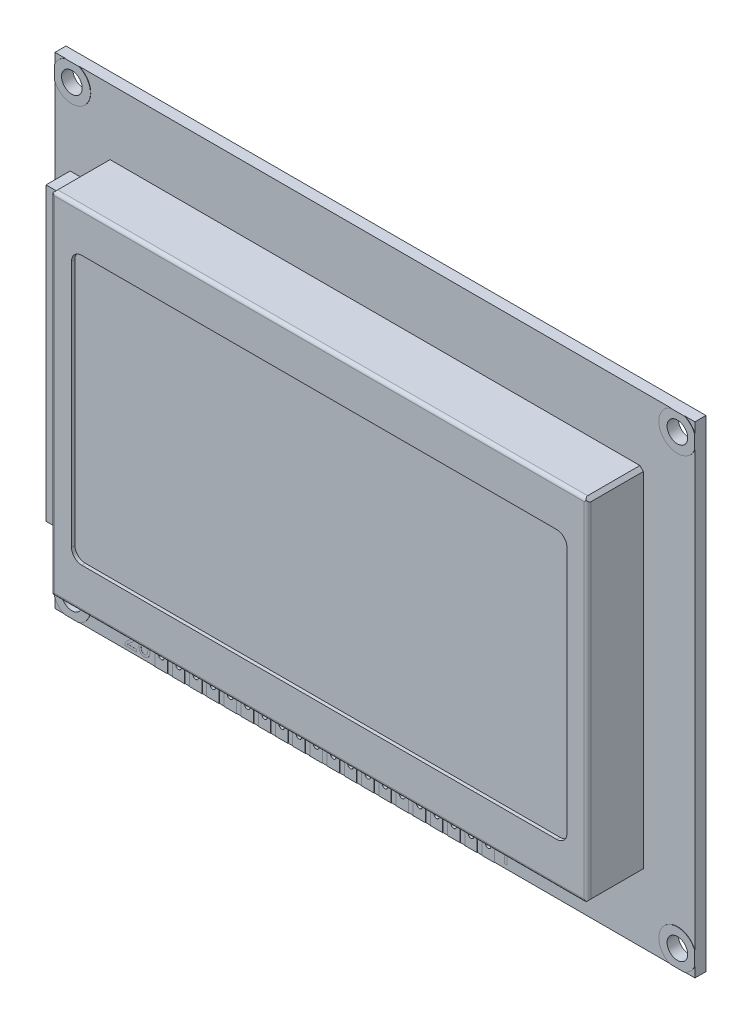
SolidWorks part; units mm, degrees
ref_plane "Front Plane" through (0, 0, 0) normal (0, 0, 1) x (1, 0, 0)
ref_plane "Top Plane" through (0, 0, 0) normal (0, 1, 0) x (1, 0, 0)
ref_plane "Right Plane" through (0, 0, 0) normal (1, 0, 0) x (0, 0, -1)
sketch "Szkic2" plane through (0, 0, 0) normal (0, 0, 1) x (1, 0, 0)
  line L1 (-46.5, -35) -> (46.5, -35)
  line L2 (-46.5, -35) -> (-46.5, 35)
  line L3 (-46.5, 35) -> (46.5, 35)
  line L4 (46.5, -35) -> (46.5, 35)
  line L5 (-46.5, -35) -> (46.5, 35) construction
  line L6 (-46.5, 35) -> (46.5, -35) construction
  circle A0 centre (-44, -32.5) radius 1.5
  circle A1 centre (44, -32.5) radius 1.5
  circle A2 centre (44, 32.5) radius 1.5
  circle A3 centre (-44, 32.5) radius 1.5
  circle A4 centre (16.5, -33.25) radius 0.4
  circle A5 centre (14, -33.25) radius 0.4
  circle A6 centre (11.5, -33.25) radius 0.4
  circle A7 centre (9, -33.25) radius 0.4
  circle A8 centre (6.5, -33.25) radius 0.4
  circle A9 centre (4, -33.25) radius 0.4
  circle A10 centre (1.5, -33.25) radius 0.4
  circle A11 centre (-1, -33.25) radius 0.4
  circle A12 centre (-3.5, -33.25) radius 0.4
  circle A13 centre (-6, -33.25) radius 0.4
  circle A14 centre (-8.5, -33.25) radius 0.4
  circle A15 centre (-11, -33.25) radius 0.4
  circle A16 centre (-13.5, -33.25) radius 0.4
  circle A17 centre (-16, -33.25) radius 0.4
  circle A18 centre (-18.5, -33.25) radius 0.4
  circle A19 centre (-21, -33.25) radius 0.4
  circle A20 centre (-23.5, -33.25) radius 0.4
  circle A21 centre (-26, -33.25) radius 0.4
  circle A22 centre (-28.5, -33.25) radius 0.4
  circle A23 centre (-31, -33.25) radius 0.4
  point P0 (0, 0)
  dimension "D3" = 2.5
  dimension "D4" = 2.5
  dimension "D5" = 3
  dimension "D6" = 0.8
  dimension "D1" = 93
  dimension "D2" = 70
  dimension "D7" = 30
  dimension "D8" = 1.75
  dimension "D9" = 20
extrude "Dodanie-wyciągnięcie1" add sketch "Szkic2" along normal blind 1.6
sketch "Szkic3" plane through (0, 0, 1.6) normal (0, 0, 1) x (1, 0, 0)
  line L0 (-46.5, -35) -> (46.5, -35) construction
  line L1 (-31.9, -35) -> (-30.1, -35)
  line L2 (-31.9, -35) -> (-31.9, -33.25)
  line L3 (-27.6, -35) -> (-27.6, -33.25)
  line L4 (-30.1, -35) -> (-30.1, -33.25)
  line L5 (-29.4, -35) -> (-27.6, -35)
  line L6 (-29.4, -35) -> (-29.4, -33.25)
  line L7 (-25.1, -35) -> (-25.1, -33.25)
  line L8 (-26.9, -35) -> (-25.1, -35)
  line L9 (-26.9, -35) -> (-26.9, -33.25)
  line L10 (-22.6, -35) -> (-22.6, -33.25)
  line L11 (-24.4, -35) -> (-22.6, -35)
  line L12 (-24.4, -35) -> (-24.4, -33.25)
  line L13 (-20.1, -35) -> (-20.1, -33.25)
  line L14 (-21.9, -35) -> (-20.1, -35)
  line L15 (-21.9, -35) -> (-21.9, -33.25)
  line L16 (-17.6, -35) -> (-17.6, -33.25)
  line L17 (-19.4, -35) -> (-17.6, -35)
  line L18 (-19.4, -35) -> (-19.4, -33.25)
  line L19 (-15.1, -35) -> (-15.1, -33.25)
  line L20 (-16.9, -35) -> (-15.1, -35)
  line L21 (-16.9, -35) -> (-16.9, -33.25)
  line L22 (-12.6, -35) -> (-12.6, -33.25)
  line L23 (-14.4, -35) -> (-12.6, -35)
  line L24 (-14.4, -35) -> (-14.4, -33.25)
  line L25 (-10.1, -35) -> (-10.1, -33.25)
  line L26 (-11.9, -35) -> (-10.1, -35)
  line L27 (-11.9, -35) -> (-11.9, -33.25)
  line L28 (-7.6, -35) -> (-7.6, -33.25)
  line L29 (-9.4, -35) -> (-7.6, -35)
  line L30 (-9.4, -35) -> (-9.4, -33.25)
  line L31 (-5.1, -35) -> (-5.1, -33.25)
  line L32 (-6.9, -35) -> (-5.1, -35)
  line L33 (-6.9, -35) -> (-6.9, -33.25)
  line L34 (-2.6, -35) -> (-2.6, -33.25)
  line L35 (-4.4, -35) -> (-2.6, -35)
  line L36 (-4.4, -35) -> (-4.4, -33.25)
  line L37 (-0.1, -35) -> (-0.1, -33.25)
  line L38 (-1.9, -35) -> (-0.1, -35)
  line L39 (-1.9, -35) -> (-1.9, -33.25)
  line L40 (2.4, -35) -> (2.4, -33.25)
  line L41 (0.6, -35) -> (2.4, -35)
  line L42 (0.6, -35) -> (0.6, -33.25)
  line L43 (4.9, -35) -> (4.9, -33.25)
  line L44 (3.1, -35) -> (4.9, -35)
  line L45 (3.1, -35) -> (3.1, -33.25)
  line L46 (7.4, -35) -> (7.4, -33.25)
  line L47 (5.6, -35) -> (7.4, -35)
  line L48 (5.6, -35) -> (5.6, -33.25)
  line L49 (9.9, -35) -> (9.9, -33.25)
  line L50 (8.1, -35) -> (9.9, -35)
  line L51 (8.1, -35) -> (8.1, -33.25)
  line L52 (12.4, -35) -> (12.4, -33.25)
  line L53 (10.6, -35) -> (12.4, -35)
  line L54 (10.6, -35) -> (10.6, -33.25)
  line L55 (14.9, -35) -> (14.9, -33.25)
  line L56 (13.1, -35) -> (14.9, -35)
  line L57 (13.1, -35) -> (13.1, -33.25)
  line L58 (17.4, -35) -> (17.4, -33.25)
  line L59 (15.6, -35) -> (17.4, -35)
  line L60 (15.6, -35) -> (15.6, -33.25)
  arc A1 (-27.6, -33.25) -> (-29.4, -33.25) centre (-28.5, -33.25) ccw
  circle A2 centre (-44, 32.5) radius 2.7
  circle A3 centre (-44, 32.5) radius 2.7
  circle A4 centre (-31, -33.25) radius 0.9
  arc A5 (-30.1, -33.25) -> (-31.9, -33.25) centre (-31, -33.25) ccw
  arc A6 (-25.1, -33.25) -> (-26.9, -33.25) centre (-26, -33.25) ccw
  arc A7 (-22.6, -33.25) -> (-24.4, -33.25) centre (-23.5, -33.25) ccw
  arc A8 (-20.1, -33.25) -> (-21.9, -33.25) centre (-21, -33.25) ccw
  arc A9 (-17.6, -33.25) -> (-19.4, -33.25) centre (-18.5, -33.25) ccw
  arc A10 (-15.1, -33.25) -> (-16.9, -33.25) centre (-16, -33.25) ccw
  arc A11 (-12.6, -33.25) -> (-14.4, -33.25) centre (-13.5, -33.25) ccw
  arc A12 (-10.1, -33.25) -> (-11.9, -33.25) centre (-11, -33.25) ccw
  circle A13 centre (44, 32.5) radius 2.7
  circle A14 centre (44, 32.5) radius 2.7
  arc A15 (-7.6, -33.25) -> (-9.4, -33.25) centre (-8.5, -33.25) ccw
  circle A16 centre (44, -32.5) radius 2.7
  circle A17 centre (44, -32.5) radius 2.7
  circle A19 centre (-44, -32.5) radius 2.7
  circle A20 centre (-44, -32.5) radius 2.7
  arc A21 (-5.1, -33.25) -> (-6.9, -33.25) centre (-6, -33.25) ccw
  arc A22 (-2.6, -33.25) -> (-4.4, -33.25) centre (-3.5, -33.25) ccw
  arc A23 (-0.1, -33.25) -> (-1.9, -33.25) centre (-1, -33.25) ccw
  arc A24 (2.4, -33.25) -> (0.6, -33.25) centre (1.5, -33.25) ccw
  arc A25 (4.9, -33.25) -> (3.1, -33.25) centre (4, -33.25) ccw
  arc A26 (7.4, -33.25) -> (5.6, -33.25) centre (6.5, -33.25) ccw
  arc A27 (9.9, -33.25) -> (8.1, -33.25) centre (9, -33.25) ccw
  arc A28 (12.4, -33.25) -> (10.6, -33.25) centre (11.5, -33.25) ccw
  arc A29 (14.9, -33.25) -> (13.1, -33.25) centre (14, -33.25) ccw
  arc A30 (17.4, -33.25) -> (15.6, -33.25) centre (16.5, -33.25) ccw
  circle M6 centre (-28.5, -33.25) radius 0.4
  circle M7 centre (-23.5, -33.25) radius 0.4
  circle M8 centre (-18.5, -33.25) radius 0.4
  circle M9 centre (-13.5, -33.25) radius 0.4
  circle M10 centre (-8.5, -33.25) radius 0.4
  circle M11 centre (-3.5, -33.25) radius 0.4
  circle M12 centre (1.5, -33.25) radius 0.4
  circle M13 centre (6.5, -33.25) radius 0.4
  circle M14 centre (11.5, -33.25) radius 0.4
  circle M15 centre (-44, 32.5) radius 1.5
  circle M16 centre (44, -32.5) radius 1.5
  circle M17 centre (-44, -32.5) radius 1.5
  line M18 (46.5, -35) -> (46.5, 35)
  line M19 (46.5, 35) -> (-46.5, 35)
  line M20 (-46.5, 35) -> (-46.5, -35)
  line M21 (-46.5, -35) -> (46.5, -35)
  circle M22 centre (16.5, -33.25) radius 0.4
  circle M23 centre (44, 32.5) radius 1.5
  circle M24 centre (14, -33.25) radius 0.4
  circle M25 centre (9, -33.25) radius 0.4
  circle M26 centre (4, -33.25) radius 0.4
  circle M27 centre (-1, -33.25) radius 0.4
  circle M28 centre (-6, -33.25) radius 0.4
  circle M29 centre (-11, -33.25) radius 0.4
  circle M30 centre (-16, -33.25) radius 0.4
  circle M31 centre (-21, -33.25) radius 0.4
  circle M32 centre (-26, -33.25) radius 0.4
  circle M33 centre (-31, -33.25) radius 0.4
  dimension "D1" = 1.2
  dimension "D2" = 1.2
  dimension "D3" = 1.2
  dimension "D4" = 1.2
  dimension "D5" = 0.5
  dimension "D6" = 20
extrude "Dodanie-wyciągnięcie2" add sketch "Szkic3" along normal blind 0.05 contours A20 M20 M21 M17 | L4 A5 L2 M21 M33 | L3 A1 L6 M21 M6 | L7 A6 L9 M21 M32 | L10 A7 L12 M21 M7 | L13 A8 L15 M21 M31 | L16 A9 L18 M21 M8 | L19 A10 L21 M21 M30 | L22 A11 L24 M21 M9 | L25 A12 L27 M21 M29 | L28 A15 L30 M21 M10 | L31 A21 L33 M21 M28 | L34 A22 L36 M21 M11 | L37 A23 L39 M21 M27 | L40 A24 L42 M21 M12 | L43 A25 L45 M21 M26 | L46 A26 L48 M21 M13 | L49 A27 L51 M21 M25 | L52 A28 L54 M21 M14 | L55 A29 L57 M21 M24 | L58 A30 L60 M21 M22 | A17 M18 M21 M16 | A14 M18 M19 M23 | A3 M19 M20 M15 region at (-31, -34.4591, 1.6) region at (-31, -32.3755, 1.6) region at (-44, -34.9265, 1.6) region at (-28.5, -33.8292, 1.6) region at (-26, -33.8292, 1.6) region at (-46.4265, 32.5, 1.6) region at (-23.5, -33.8292, 1.6) region at (44, 34.9265, 1.6) region at (-21, -33.8292, 1.6) region at (46.4265, -32.5, 1.6) region at (-18.5, -33.8292, 1.6) region at (16.5, -33.8292, 1.6) region at (-16, -33.8292, 1.6) region at (14, -33.8292, 1.6) region at (-13.5, -33.8292, 1.6) region at (11.5, -33.8292, 1.6) region at (-11, -33.8292, 1.6) region at (9, -33.8292, 1.6) region at (-8.5, -33.8292, 1.6) region at (6.5, -33.8292, 1.6) region at (-6, -33.8292, 1.6) region at (4, -33.8292, 1.6) region at (-3.5, -33.8292, 1.6) region at (1.5, -33.8292, 1.6) region at (-1, -33.8292, 1.6)
sketch "Szkic5" plane through (0, 0, 1.6) normal (0, 0, 1) x (1, 0, 0)
  line L0 (-38.2021, 23) -> (37.4908, 23) construction
  line L1 (39, -25.5) -> (-39, -25.5)
  line L2 (39, -25.5) -> (39, 25.5)
  line L3 (39, 25.5) -> (-39, 25.5)
  line L4 (-39, -25.5) -> (-39, 25.5)
  line L5 (39, -25.5) -> (-39, 25.5) construction
  line L6 (39, 25.5) -> (-39, -25.5) construction
  line L7 (0, 0) -> (0, 37.6904) construction
  line L8 (-48.597, 0) -> (63.6473, 0) construction
  line L9 (38, 21.5) -> (-38, 21.5)
  line L10 (38, 21.5) -> (38, 24.5)
  line L11 (38, 24.5) -> (-38, 24.5)
  line L12 (-38, 21.5) -> (-38, 24.5)
  line L13 (38, 21.5) -> (-38, 24.5) construction
  line L14 (38, 24.5) -> (-38, 21.5) construction
  line L15 (38, -21.5) -> (38, -24.5)
  line L16 (-38, -21.5) -> (-38, -24.5)
  line L17 (38, -21.5) -> (-38, -21.5)
  line L18 (38, -24.5) -> (-38, -24.5)
  line L19 (38.5, 25) -> (-38.5, 25)
  line L20 (-38.5, -25) -> (-38.5, 25)
  line L21 (38.5, -25) -> (-38.5, -25)
  line L22 (38.5, -25) -> (38.5, 25)
  point P0 (0, 0)
  point P10 (0, 23)
  dimension "D1" = 51
  dimension "D2" = 78
  dimension "D3" = 23
  dimension "D4" = 3
  dimension "D5" = 76
  dimension "D6" = 0.5
extrude "Dodanie-wyciągnięcie3" add sketch "Szkic5" along normal blind 5.5 contours L18 L15 L17 L16 | L9 L12 L11 L10 region at (0, -23, 1.6)
extrude "Dodanie-wyciągnięcie4" add sketch "Szkic5<3>" along normal blind 7.6 contours L4 L1 L2 L3 L22 L21 L20 L19 region at (0, -25.4068, 1.6)
sketch "Szkic5<3>" plane through (0, 0, 1.6) normal (0, 0, 1) x (1, 0, 0) same geometry as "Szkic5"
sketch "Szkic6" plane through (-39, 0, 0) normal (-1, 0, 0) x (0, 0, 1)
  line L0 (1.6, 31.4802) -> (1.6, -31.4802) construction
  line L1 (1.6, 24.4798) -> (5.2, 24.4798)
  line L2 (1.6, 24.4798) -> (1.6, -24.5202)
  line L3 (1.6, -24.5202) -> (5.2, -24.5202)
  line L4 (5.2, 24.4798) -> (5.2, -24.5202)
  line L5 (9.2, -25.5) -> (1.6, -25.5) construction
  point P6 (5.4, -25.5)
  dimension "D1" = 49
  dimension "D2" = 3.6
  dimension "D3" = 1
extrude "Wytnij-wyciągnięcie1" cut sketch "Szkic6" against normal up to next
sketch "Szkic7" plane through (0, 0, 1.6) normal (0, 0, 1) x (1, 0, 0)
  line L0 (-46.5, 31.4802) -> (-46.5, -31.4802) construction
  line L1 (-44.3, 21.1708) -> (37.7, 21.1708)
  line L2 (-44.3, 21.1708) -> (-44.3, -21.1708)
  line L3 (-44.3, -21.1708) -> (37.7, -21.1708)
  line L4 (37.7, 21.1708) -> (37.7, -21.1708)
  line L5 (-44.3, 21.1708) -> (37.7, -21.1708) construction
  line L6 (-44.3, -21.1708) -> (37.7, 21.1708) construction
  point P0 (-3.3, 0)
  dimension "D1" = 82
  dimension "D2" = 2.2
extrude "Dodanie-wyciągnięcie5" add sketch "Szkic7" along normal blind 3.5
sketch "Szkic8" plane through (0, 0, 7.1) normal (0, 0, 1) x (1, 0, 0)
  line L1 (-38, 24.5) -> (38, 24.5)
  line L2 (-38, 24.5) -> (-38, -24.5)
  line L3 (-38, -24.5) -> (38, -24.5)
  line L4 (38, 24.5) -> (38, -24.5)
extrude "Dodanie-wyciągnięcie6" add sketch "Szkic8" along normal up to vertex (2.1 mm away) up to point (-38.5, 25, 9.2)
sketch "Szkic9" plane through (0, 0, 9.2) normal (0, 0, 1) x (1, 0, 0)
  line L1 (-39, 25.5) -> (39, 25.5)
  line L2 (-39, 25.5) -> (-39, -25.5)
  line L3 (-39, -25.5) -> (39, -25.5)
  line L4 (39, 25.5) -> (39, -25.5)
  line L5 (34.5, -19.5) -> (-34.5, -19.5)
  line L6 (36, -18) -> (36, 18)
  line L7 (34.5, 19.5) -> (-34.5, 19.5)
  line L8 (-36, -18) -> (-36, 18)
  line L9 (36, -19.5) -> (-36, 19.5) construction
  line L10 (36, 19.5) -> (-36, -19.5) construction
  arc A0 (-34.5, -19.5) -> (-36, -18) centre (-34.5, -18) cw
  arc A1 (34.5, -19.5) -> (36, -18) centre (34.5, -18) ccw
  arc A2 (36, 18) -> (34.5, 19.5) centre (34.5, 18) ccw
  arc A3 (-34.5, 19.5) -> (-36, 18) centre (-34.5, 18) ccw
  point P6 (0, 0)
  dimension "D3" = 1.5
  dimension "D1" = 72
  dimension "D2" = 39
extrude "Dodanie-wyciągnięcie7" add sketch "Szkic9" along normal blind 0.5
sketch "Szkic10" plane through (0, 0, 1.6) normal (0, 0, 1) x (1, 0, 0)
  text T0 "20" font "Arial" height in points 10
extrude "Dodanie-wyciągnięcie8" add sketch "Szkic10" along normal blind 0.01
sketch "Szkic11" plane through (0, 0, 1.6) normal (0, 0, 1) x (1, 0, 0)
  text T0 "1" font "Arial" height in points 10
extrude "Dodanie-wyciągnięcie9" add sketch "Szkic11" along normal blind 0.01
sketch "Szkic13" plane through (0, 0, 5.1) normal (0, 0, 1) x (1, 0, 0)
  line L1 (-37.8601, 24.084) -> (37.86, 24.084)
  line L2 (-37.8601, 24.084) -> (-37.8601, -23.8914)
  line L3 (-37.8601, -23.8914) -> (37.86, -23.8914)
  line L4 (37.86, 24.084) -> (37.86, -23.8914)
extrude "Dodanie-wyciągnięcie10" add sketch "Szkic13" along normal blind 0.05
chamfer "Sfazowanie1" distance 0.5 angle 45 4 edges at (-39, -25.5, 5.65) (39, -25.5, 5.65) (39, 25.5, 5.65) (-39, 25.5, 5.65)
fillet "Zaokrąglenie1" radius 0.5 4 edges at (39, 0, 9.7) (-39, 0, 9.7) (0, -25.5, 9.7) (0, 25.5, 9.7)
sketch "Szkic14" plane through (0, 0, 1.6) normal (0, 0, 1) x (1, 0, 0)
  line L0 (17.4, -31.4904) -> (17.4, -26.3572) construction
  line L1 (14.9, -31.4904) -> (14.9, -27.4904) construction
  line L2 (-32.2396, -31.4904) -> (17.4, -31.4904) construction
  line L3 (12.372, -31.4904) -> (12.372, -26.3572) construction
  line L4 (9.7878, -31.4904) -> (9.7878, -26.3572) construction
  line L5 (7.4076, -31.4904) -> (7.4076, -26.3572) construction
  line L6 (4.8234, -31.4904) -> (4.8234, -26.3572) construction
  line L7 (2.3752, -31.4904) -> (2.3752, -26.3572) construction
  line L8 (-0.1248, -31.4904) -> (-0.1248, -26.3572) construction
  line L9 (-2.6248, -31.4904) -> (-2.6248, -26.3572) construction
  line L10 (-5.1248, -31.4904) -> (-5.1248, -26.3572) construction
  line L11 (-7.6248, -31.4904) -> (-7.6248, -26.3572) construction
  line L12 (-10.1248, -31.4904) -> (-10.1248, -26.3572) construction
  line L13 (-12.6248, -31.4904) -> (-12.6248, -26.3572) construction
  line L14 (-15.1248, -31.4904) -> (-15.1248, -26.3572) construction
  line L15 (-17.6248, -31.4904) -> (-17.6248, -26.3572) construction
  line L16 (-20.1248, -31.4904) -> (-20.1248, -26.3572) construction
  line L17 (-22.6248, -31.4904) -> (-22.6248, -26.3572) construction
  line L18 (-25.1248, -31.4904) -> (-25.1248, -26.3572) construction
  line L19 (-27.6248, -31.4904) -> (-27.6248, -26.3572) construction
  line L20 (-30.1248, -31.4904) -> (-30.1248, -26.3572) construction
  text T0 "VSS" font "Arial" height 1.5
  text T1 "VDD" font "Arial" height 1.5
  text T2 "V0" font "Arial" height 1.5
  text T3 "RS" font "Arial" height 1.5
  text T4 "R/W" font "Arial" height 1.5
  text T5 "E" font "Arial" height 1.5
  text T6 "DB0" font "Arial" height 1.5
  text T7 "DB1" font "Arial" height 1.5
  text T8 "DB2" font "Arial" height 1.5
  text T9 "DB3" font "Arial" height 1.5
  text T10 "DB4" font "Arial" height 1.5
  text T11 "DB5" font "Arial" height 1.5
  text T12 "DB6" font "Arial" height 1.5
  text T13 "DB7" font "Arial" height 1.5
  text T14 "PSB" font "Arial" height 1.5
  text T15 "NC" font "Arial" height 1.5
  text T16 "RST" font "Arial" height 1.5
  text T17 "VOUT\r\n" font "Arial" height 1.5
  text T18 "BLA" font "Arial" height 1.5
  text T19 "BLK" font "Arial" height 1.5
  dimension "D1" = 14
extrude "Dodanie-wyciągnięcie11" add sketch "Szkic14" along normal blind 0.02
